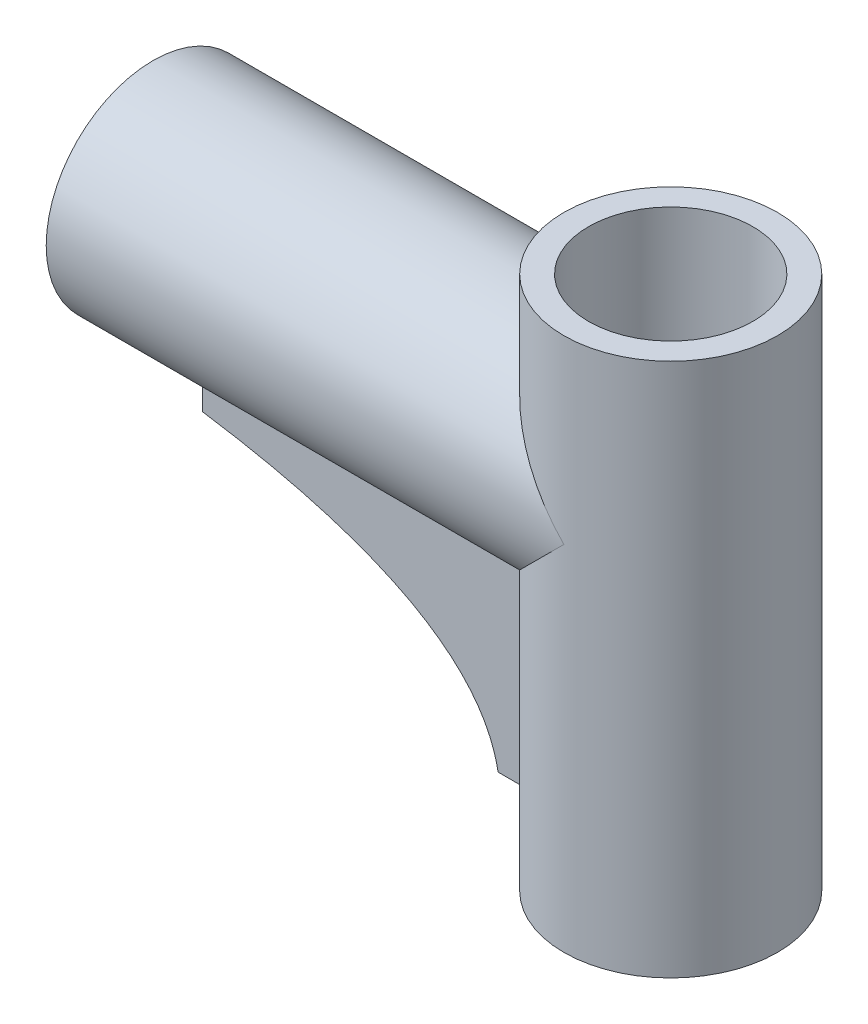
SolidWorks part; units mm, degrees
ref_plane "Front Plane" through (0, 0, 0) normal (0, 0, 1) x (1, 0, 0)
ref_plane "Top Plane" through (0, 0, 0) normal (0, 1, 0) x (1, 0, 0)
ref_plane "Right Plane" through (0, 0, 0) normal (1, 0, 0) x (0, 0, -1)
sketch "Buitencirkel" plane through (0, 0, 0) normal (0, 1, 0) x (1, 0, 0)
  circle A1 centre (0, 0) radius 13
  dimension "D2" = 26
extrude "Cilinder basis" add sketch "Buitencirkel" along normal blind 65
ref_plane "Plane2" through (0, 0, 0) normal (0, -1, 0) x (-1, 0, 0)
sketch "Binnencirkel motor" plane through (0, 0, 0) normal (0, -1, 0) x (-1, 0, 0)
  circle A0 centre (0, 0) radius 11
  dimension "D1" = 22
extrude "Holte motor" cut sketch "Binnencirkel motor" against normal blind 25
ref_plane "Plane3" through (0, 65, 0) normal (0, 1, 0) x (1, 0, 0)
sketch "Binnencirkel buis" plane through (0, 65, 0) normal (0, 1, 0) x (1, 0, 0)
  circle A0 centre (0, 0) radius 10
  dimension "D1" = 20
extrude "Holte buis" cut sketch "Binnencirkel buis" against normal blind 35
ref_plane "Plane4" through (0, 25, 0) normal (0, -1, 0) x (-1, 0, 0)
sketch "Cirkel motoras" plane through (0, 25, 0) normal (0, -1, 0) x (-1, 0, 0)
  line L0 (0, 2.85) -> (0, -2.85) construction
  line L1 (-11, 0) -> (11, 0) construction
  line L2 (2.35, -1.6125) -> (2.35, 1.6125)
  circle A0 centre (0, 0) radius 11 construction
  arc A1 (2.35, 1.6125) -> (2.35, -1.6125) centre (0, 0) ccw
  point P9 (0, 0)
  point P13 (0, 0)
  dimension "D1" = 5.7
  dimension "D2" = 2.35
extrude "Uitsparing motoras" cut sketch "Cirkel motoras" against normal through all contours A1 L2
sketch "Cirkel motorpinnetjes" plane through (0, 25, 0) normal (0, -1, 0) x (-1, 0, 0)
  line L0 (0, 2.85) -> (0, -2.85) construction
  line L1 (-5.5, 0) -> (5.5, 0) construction
  circle A0 centre (-5.5, 0) radius 0.9
  arc A1 (2.35, 1.6125) -> (2.35, -1.6125) centre (0, 0) ccw construction
  circle A2 centre (0, 0) radius 5.5 construction
  circle A3 centre (5.5, 0) radius 0.9
  point P10 (0, 0)
  point P14 (0, 0)
  dimension "D1" = 1.8
  dimension "D2" = 11
extrude "Uitsparingen motorpinnetjes" add sketch "Cirkel motorpinnetjes" along normal blind 2
sketch "Cirkel polen" plane through (0, 25, 0) normal (0, -1, 0) x (-1, 0, 0)
  line L0 (0, 0) -> (0, -11) construction
  line L1 (0, 0) -> (11, 0) construction
  circle A0 centre (0, 0) radius 11 construction
  circle A2 centre (0, -7.55) radius 2.45
  circle A3 centre (0, 7.55) radius 2.45
  circle A4 centre (0, 0) radius 10 construction
  dimension "D1" = 4.9
extrude "Uitsparingen motorpolen" cut sketch "Cirkel polen" against normal through all contours A3 | A2
ref_plane "Plane5" through (-13, 0, 0) normal (-1, 0, 0) x (0, 0, 1)
sketch "Sketch2" plane through (-13, 0, 0) normal (-1, 0, 0) x (0, 0, 1)
  line L0 (13, 0) -> (13, 65) construction
  line L1 (33.5859, 65) -> (-33.5859, 65) construction
  circle A0 centre (0, 43) radius 13
  dimension "D1" = 26
  dimension "D2" = 22
extrude "Boss-Extrude1" add sketch "Sketch2" along normal blind 50 and the other way up to surface other way up to face at (0, 65, 13)
sketch "Sketch3" plane through (-63, 0, 0) normal (-1, 0, 0) x (0, 0, 1)
  circle A0 centre (0, 43) radius 10
  circle A1 centre (0, 43) radius 13 construction
  dimension "D1" = 20
extrude "Cut-Extrude1" cut sketch "Sketch3" against normal blind 40
sketch "Sketch4" plane through (-23, 0, 0) normal (-1, 0, 0) x (0, 0, 1)
  circle A0 centre (0, 43) radius 7
  circle A1 centre (0, 43) radius 10 construction
  dimension "D1" = 14
extrude "Cut-Extrude2" cut sketch "Sketch4" against normal up to surface (15.8586 mm away) up to face at (0, 30, 0)
sketch "Sketch5" plane through (0, 0, 0) normal (0, 0, 1) x (1, 0, 0)
  line L0 (-52, 27) -> (-16, 27)
  line L2 (-16, 27) -> (-16, 7)
  line L5 (-63, 30) -> (-13, 30) construction
  line L6 (-13, 30) -> (-13, 0) construction
  spline S0 degree 2 poles (-52, 27) (-18.7804, 22.0223) (-16, 7) knots 0 0 0 1 1 1
  point P2 (-13, 27.7669)
  point P3 (-15.4947, 27.1874)
  point P6 (-15.4947, 8.181)
  point P7 (-13, 27.3613)
  dimension "D1" = 36
  dimension "D2" = 20
  dimension "D3" = 3
  dimension "D4" = 3
extrude "Boss-Extrude2" add sketch "Sketch5" along normal blind 5 and the other way blind 5 separate body
sketch "Sketch11" plane through (0, 27, 0) normal (0, 1, 0) x (1, 0, 0)
  line L1 (-52, 5) -> (-16, 5)
  line L2 (-52, 5) -> (-52, -5)
  line L3 (-52, -5) -> (-16, -5)
  line L4 (-16, 5) -> (-16, -5)
extrude "Boss-Extrude6" add sketch "Sketch11" along normal up to surface (4 mm away) up to face at (-63, 43, 13)
sketch "Sketch12" plane through (-16, 0, 0) normal (1, 0, 0) x (0, 0, -1)
  line L1 (-5, 7) -> (5, 7)
  line L2 (-5, 7) -> (-5, 31)
  line L3 (-5, 31) -> (5, 31)
  line L4 (5, 7) -> (5, 31)
extrude "Boss-Extrude7" add sketch "Sketch12" along normal up to surface (4 mm away) up to face at (0, 0, 13)
